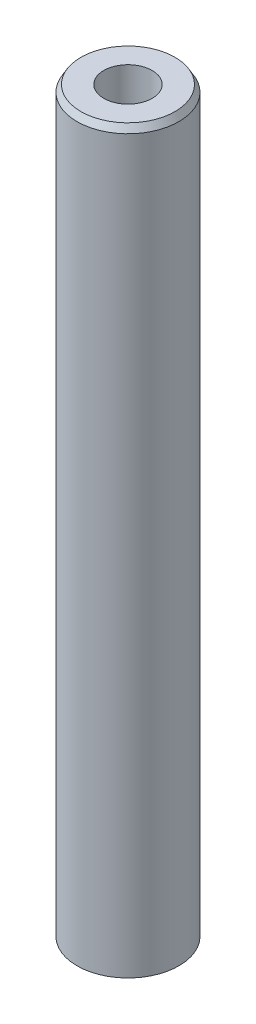
SolidWorks part; units mm, degrees
ref_plane "Front Plane" through (0, 0, 0) normal (0, 0, 1) x (1, 0, 0)
ref_plane "Top Plane" through (0, 0, 0) normal (0, 1, 0) x (1, 0, 0)
ref_plane "Right Plane" through (0, 0, 0) normal (1, 0, 0) x (0, 0, -1)
sketch "Sketch1" plane through (0, 0, 0) normal (0, 1, 0) x (1, 0, 0)
  circle A0 centre (0, 0) radius 20
  dimension "SHAFT_OD" = 40
extrude "Boss-Extrude1" add sketch "Sketch1" along normal blind 291.1762
sketch "Sketch2" plane through (0, 0, 0) normal (0, 1, 0) x (1, 0, 0)
  circle A0 centre (0, 0) radius 9.4967
  dimension "BORE_D" = 18.9935
extrude "Cut-Extrude1" cut sketch "Sketch2" along normal through all
chamfer "Chamfer1" distance 2.6495 angle 30 2 edges at (0, 291.1762, 20) (0, 0, 20) first distance on face at (0, 291.1762, 20) first distance on face at (0, 0, 9.4967)
